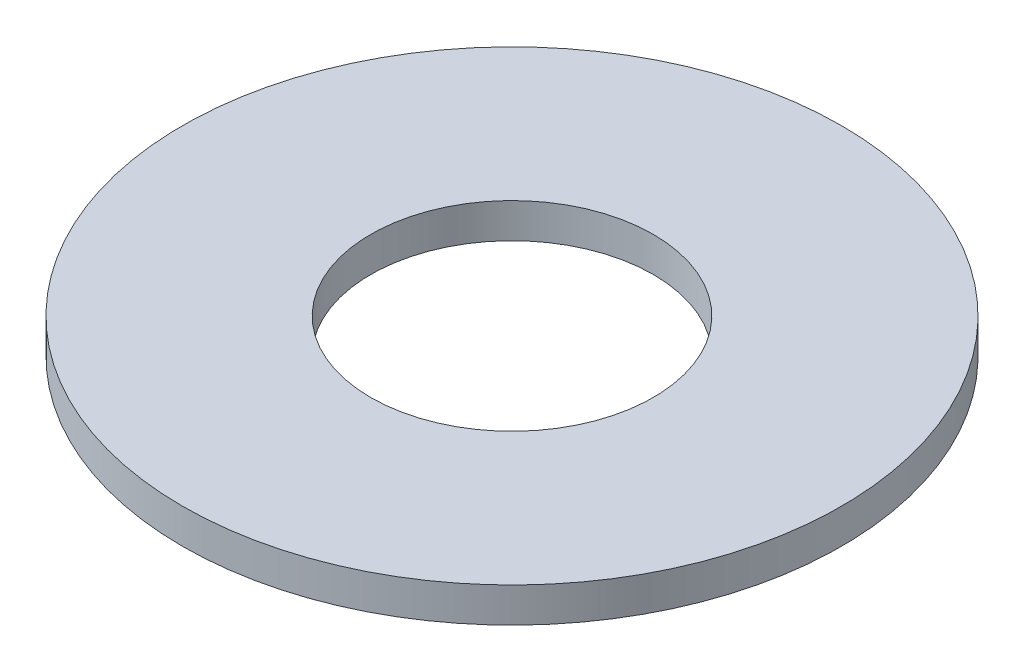
SolidWorks part; units mm, degrees
ref_plane "Front Plane" through (0, 0, 0) normal (0, 0, 1) x (1, 0, 0)
ref_plane "Top Plane" through (0, 0, 0) normal (0, 1, 0) x (1, 0, 0)
ref_plane "Right Plane" through (0, 0, 0) normal (1, 0, 0) x (0, 0, -1)
sketch "Sketch1" plane through (0, 0, 0) normal (0, 1, 0) x (1, 0, 0)
  circle A0 centre (0, 0) radius 37.9
  circle A1 centre (0, 0) radius 16.25
  dimension "D1" = 32.5
  dimension "D2" = 75.8
extrude "Boss-Extrude1" add sketch "Sketch1" along normal blind 4
